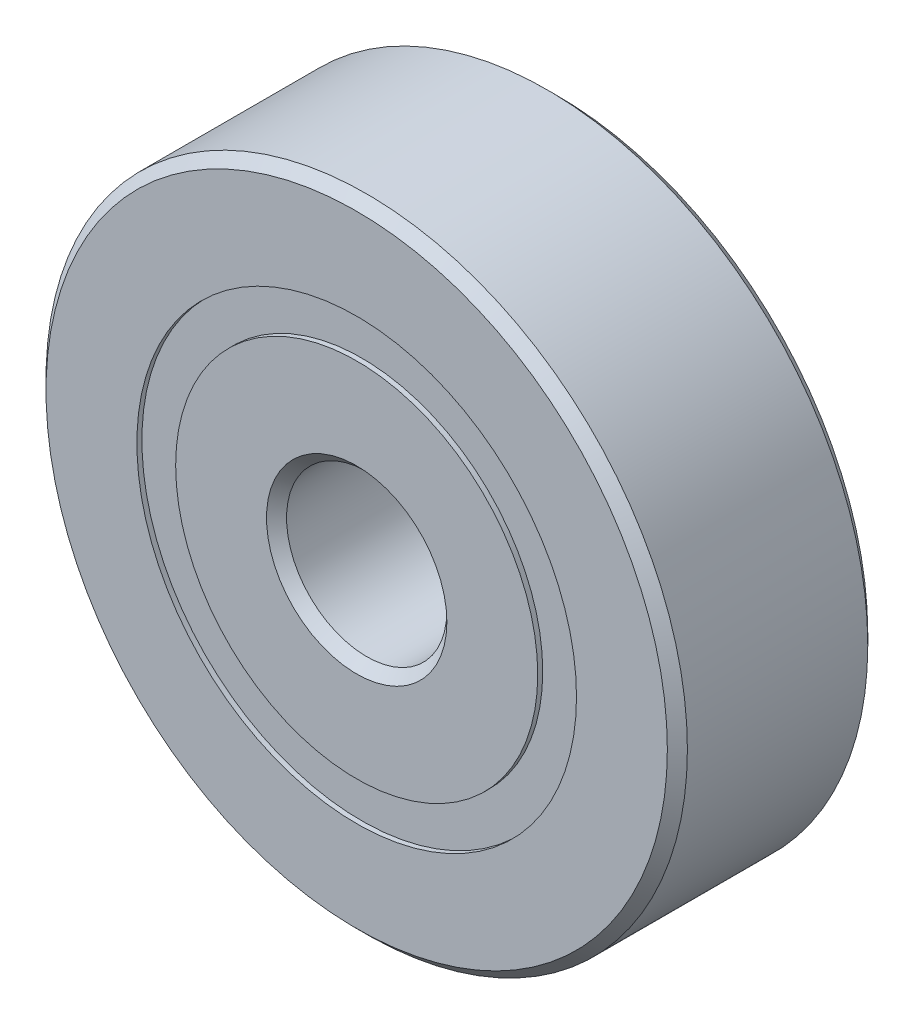
SolidWorks part; units mm, degrees
ref_plane "Front Plane" through (0, 0, 0) normal (0, 0, 1) x (1, 0, 0)
ref_plane "Top Plane" through (0, 0, 0) normal (0, 1, 0) x (1, 0, 0)
ref_plane "Right Plane" through (0, 0, 0) normal (1, 0, 0) x (0, 0, -1)
sketch "Sketch1" plane through (0, 0, 0) normal (1, 0, 0) x (0, 0, -1)
  line L0 (-2.5, 0) -> (2.5, 0) construction
  line L1 (0, 8) -> (0, -8) construction
  line L2 (2.25, 8) -> (-2.25, 8)
  line L3 (-2.25, 8) -> (-2.5, 7.75)
  line L4 (-2.5, 7.75) -> (-2.5, 5.4835)
  line L5 (-2.5, 5.4835) -> (-1.1111, 5.4835)
  line L6 (2.5, 5.4835) -> (1.1111, 5.4835)
  line L7 (2.5, 7.75) -> (2.5, 5.4835)
  line L8 (2.25, 8) -> (2.5, 7.75)
  line L9 (0, 8) -> (0, 5) construction
  line L10 (0, 5) -> (0, 2) construction
  arc A0 (-1.1111, 5.4835) -> (1.1111, 5.4835) centre (0, 5) cw
  point P14 (0, 2)
  dimension "Width" = 5
  dimension "OD" = 16
  dimension "D1" = 45
  dimension "D2" = 0.25
  dimension "Shaft Dia" = 4
  dimension "D3" = 2.2222
  dimension "D4" = 0.4835
revolve "Revolve1" add sketch "Sketch1" angle 360 about L0
sketch "Sketch3" plane through (0, 0, 0) normal (1, 0, 0) x (0, 0, -1)
  line L0 (-2.5, 4.5165) -> (-1.1111, 4.5165)
  line L1 (0, 8) -> (0, -8) construction
  line L2 (-2.5, 7.75) -> (-2.5, 5.4835) construction
  line L3 (-2.5, 4.5165) -> (-2.5, 2.25)
  line L4 (-2.25, 8) -> (-2.5, 7.75) construction
  line L5 (-2.5, 2.25) -> (-2.25, 2)
  line L6 (-2.25, 2) -> (2.25, 2)
  line L7 (2.25, 8) -> (2.25, -8) construction
  line L8 (2.25, 2) -> (2.5, 2.25)
  line L9 (2.5, -7.75) -> (2.5, 7.75) construction
  line L10 (2.5, 2.25) -> (2.5, 4.5165)
  line L11 (2.5, 4.5165) -> (1.1111, 4.5165)
  line L13 (2.25, 8) -> (2.5, 7.75) construction
  arc A0 (1.1111, 5.4835) -> (-1.1111, 5.4835) centre (0, 5) ccw construction
  arc A1 (1.1111, 4.5165) -> (-1.1111, 4.5165) centre (0, 5) cw
revolve "Revolve3" add sketch "Sketch3" angle 360 about L0
sketch "Sketch4" plane through (0, 0, 0) normal (1, 0, 0) x (0, 0, -1)
  line L0 (-1.2118, 5) -> (1.2118, 5)
  arc A2 (-1.2118, 5) -> (1.2118, 5) centre (0, 5) cw
  arc A3 (1.1111, 5.4835) -> (-1.1111, 5.4835) centre (0, 5) ccw construction
revolve "Revolve4" add sketch "Sketch4" angle 360 about L0
ref_axis "Axis1" through (0, 0, -2.5) along (0, 0, 1)
pattern_circular "CirPattern1" count 12 over 360 about axis through (0, 0, -2.5) along (0, 0, 1) of bodies 104
sketch "Sketch5" plane through (0, 0, 0) normal (1, 0, 0) x (0, 0, -1)
  line L0 (-2.5, 5.4835) -> (-1.1111, 5.4835) construction
  line L1 (-2.375, 5.4835) -> (-1.2118, 5.4835)
  line L2 (-2.375, 5.4835) -> (-2.375, 4.5165)
  line L3 (-2.375, 4.5165) -> (-1.2118, 4.5165)
  line L4 (-1.2118, 5.4835) -> (-1.2118, 4.5165)
  line L5 (-2.5, 4.5165) -> (-1.1111, 4.5165) construction
  line L6 (2.5, 5.4835) -> (1.1111, 5.4835) construction
  line L7 (2.375, 5.4835) -> (1.2118, 5.4835)
  line L8 (2.375, 5.4835) -> (2.375, 4.5165)
  line L9 (2.375, 4.5165) -> (1.2118, 4.5165)
  line L10 (1.2118, 5.4835) -> (1.2118, 4.5165)
  line L11 (2.5, 4.5165) -> (1.1111, 4.5165) construction
  line L12 (-2.25, 8) -> (-2.5, 7.75) construction
  point P18 (-2.375, 7.875)
revolve "Revolve5" add sketch "Sketch5" angle 360 about L0
equation "\"D2@Sketch1\" = \"Width@Sketch1\"*.05"
equation "\"D3@Sketch1\" = \"Width@Sketch1\"/2.25"
equation "\"D4@Sketch1\" = (((\"OD@Sketch1\"-\"Width@Sketch1\")/2)/3.25)/3.5"
equation "\"D2@CirPattern1\" = 360/\"Balls@CirPattern1\""
